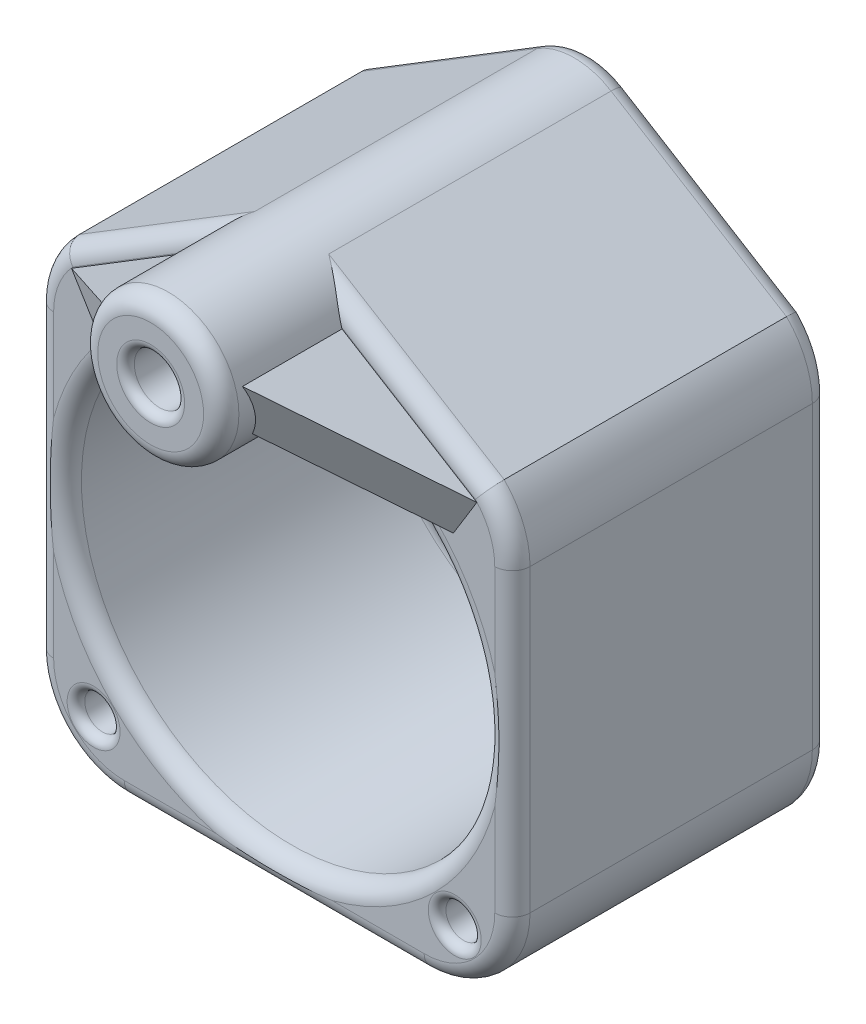
SolidWorks part; units mm, degrees
ref_plane "Plano frontal" through (0, 0, 0) normal (0, 0, 1) x (1, 0, 0)
ref_plane "Plano superior" through (0, 0, 0) normal (0, 1, 0) x (1, 0, 0)
ref_plane "Plano direito" through (0, 0, 0) normal (1, 0, 0) x (0, 0, -1)
sketch "Esboço1" plane through (0, 0, 0) normal (0, 0, 1) x (1, 0, 0)
  line L12 (8.5, -13.5) -> (-8.5, -13.5)
  line L13 (13.5, -8.5) -> (13.5, 8.5)
  line L15 (-13.5, -8.5) -> (-13.5, 8.5)
  line L16 (13.5, -13.5) -> (-13.5, 13.5) construction
  line L17 (13.5, 13.5) -> (-13.5, -13.5) construction
  line L18 (-12.0355, 12.0355) -> (-2.0913, 18.1347)
  line L19 (12.0355, 12.0355) -> (2.0913, 18.1347)
  circle A1 centre (0, 14.725) radius 1.425
  circle A17 centre (0, 0) radius 11.925
  arc A19 (13.5, 8.5) -> (12.0355, 12.0355) centre (8.5, 8.5) ccw
  arc A20 (8.5, -13.5) -> (13.5, -8.5) centre (8.5, -8.5) ccw
  arc A21 (-8.5, -13.5) -> (-13.5, -8.5) centre (-8.5, -8.5) cw
  arc A22 (2.0913, 18.1347) -> (-2.0913, 18.1347) centre (0, 14.725) ccw
  arc A23 (-12.0355, 12.0355) -> (-13.5, 8.5) centre (-8.5, 8.5) ccw
  dimension "D1" = 14.725
  dimension "D2" = 27
  dimension "D5" = 8
  dimension "D6" = 2.85
  dimension "D7" = 23.85
  dimension "D3" = 27
extrude "Ressalto-extrusão1" add sketch "Esboço1" along normal blind 18
sketch "Esboço2" plane through (0, 0, 18) normal (0, 0, 1) x (1, 0, 0)
  circle A5 centre (0, 14.725) radius 1.425
  circle A8 centre (0, 14.725) radius 4
extrude "Ressalto-extrusão3" add sketch "Esboço2" along normal blind 7
sketch3d "3DSketch1"
  line L1 (-3.5143, 14.5684, 18) -> (-9.6466, 10.8072, 18) construction
  line L3 (-9.6466, 10.8072, 18) -> (-9.6466, 10.8072, 23.0025) construction
ref_plane "Plano1" through (-7.4535, 12.1523, 0) normal (-0.5228, 0.8524, 0) x (0.8524, 0.5228, 0)
fillet "Filete1" radius 1 22 edges at (-13.1194, 10.4134, 0) (-13.5, 0, 0) (-12.0355, -12.0355, 0) (0, -13.5, 0) (12.0355, -12.0355, 0) (13.5, 0, 0) (-7.0634, 15.0851, 0) (0, 18.725, 0) (-13.1194, 10.4134, 18) (13.1194, 10.4134, 18) (13.5, 0, 18) (12.0355, -12.0355, 18) (0, -13.5, 18) (-12.0355, -12.0355, 18) (4, 14.725, 25) (11.925, 0, 0) (13.1194, 10.4134, 0) (7.0634, 15.0851, 0) (7.0634, 15.0851, 18) (-7.0634, 15.0851, 18) (-13.5, 0, 18) (0, -11.925, 18)
chamfer "Chanfro1" distance 1.2 angle 65 1 edges at (0, 10.725, 18) first distance on face at (0, 11.325, 18)
fillet "Filete2" radius 0.5 2 edges at (1.425, 14.725, 0) (1.425, 14.725, 25)
sketch "Esboço3" plane through (-7.4535, 12.1523, 0) normal (-0.5228, 0.8524, 0) x (0.8524, 0.5228, 0)
  line L0 (5.501, -18) -> (-3.9669, -18)
  line L1 (-3.9669, -18) -> (5.501, -23.9548)
  line L3 (5.501, -23.9548) -> (5.501, -18)
  line L7 (7.6987, -18) -> (-3.9669, -18) construction
extrude "Ressalto-extrusão4" add sketch "Esboço3" against normal blind 1.3 and the other way blind 1.25
mirror "Espelhar1" about plane through (0, 0, 0) normal (1, 0, 0) of "Ressalto-extrusão4"
sketch "Esboço4" plane through (0, 0, 0) normal (0, 0, -1) x (-1, 0, 0)
  line L0 (9.1394, -9.1394) -> (11.3284, -11.3284) construction
  line L1 (-9.1394, -9.1394) -> (-11.3284, -11.3284) construction
  line L2 (0, 0) -> (0, -4.5233) construction
  arc A3 (-12.5, -8.5) -> (-8.5, -12.5) centre (-8.5, -8.5) ccw construction
  circle A4 centre (-10.2339, -10.2339) radius 1
  circle A5 centre (10.2339, -10.2339) radius 1
  dimension "D1" = 2
extrude "Corte-extrusão1" cut sketch "Esboço4" against normal blind 23 and the other way blind 12
fillet "Filete3" radius 0.5 4 edges at (-9.2339, -10.2339, 0) (-9.2339, -10.2339, 18) (11.2339, -10.2339, 0) (11.2339, -10.2339, 18)
